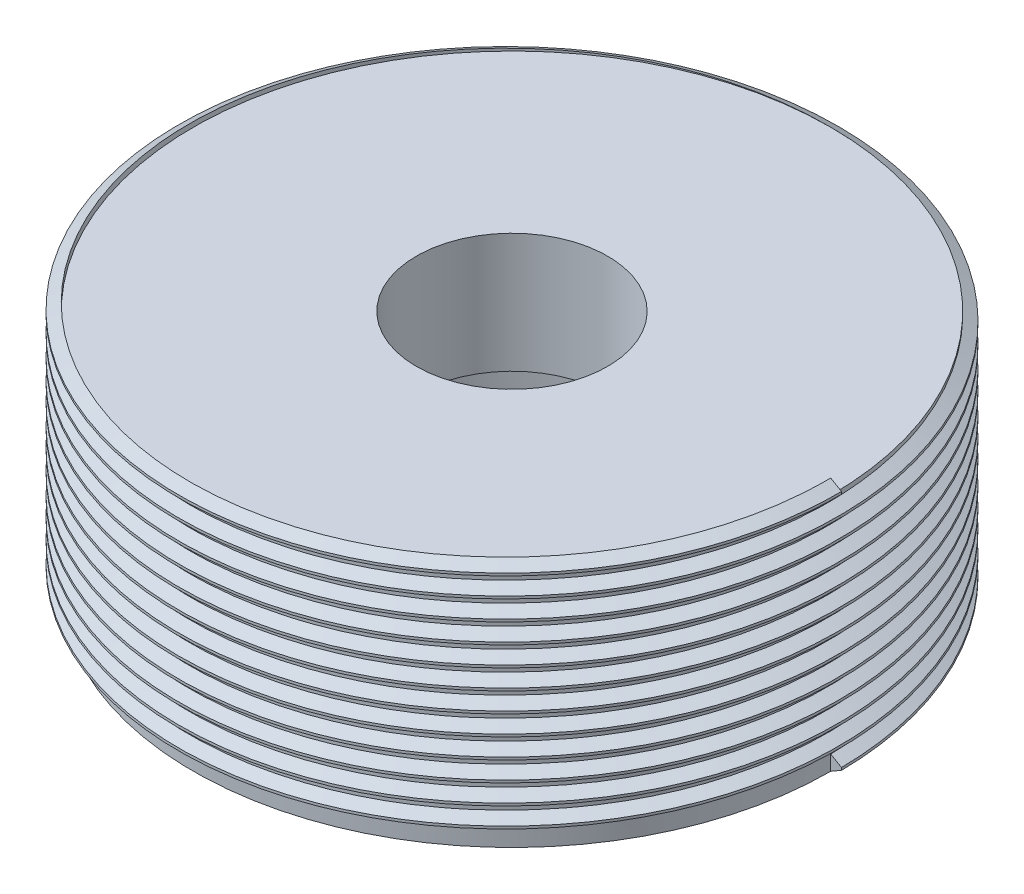
SolidWorks part; units mm, degrees
ref_plane "Front Plane" through (0, 0, 0) normal (0, 0, 1) x (1, 0, 0)
ref_plane "Top Plane" through (0, 0, 0) normal (0, 1, 0) x (1, 0, 0)
ref_plane "Right Plane" through (0, 0, 0) normal (1, 0, 0) x (0, 0, -1)
sketch "Sketch2" plane through (0, 0, 0) normal (0, 1, 0) x (1, 0, 0)
  circle A0 centre (0, 0) radius 40
extrude "Boss-Extrude1" add sketch "Sketch2" along normal blind 30
sketch "Sketch4" plane through (0, 30, 0) normal (0, 1, 0) x (1, 0, 0)
  circle A0 centre (0, 0) radius 12
extrude "Cut-Extrude1" cut sketch "Sketch4" against normal blind 15
sketch "Sketch5" plane through (0, 15, 0) normal (0, 1, 0) x (1, 0, 0)
  circle A0 centre (0, 0) radius 25
extrude "Cut-Extrude2" cut sketch "Sketch5" against normal blind 15
thread "Thread1" pitch 2.5 method extrude profile "Thread Profile1" start angle 0, offset 0, length 0, pitch 2.5, diameter 80
ref_plane "Plane1" through (40, 0, 0) normal (0, 0, 1) x (1, 0, 0)
sketch "Thread Profile1" plane through (40, 0, 0) normal (0, 0, 1) x (1, 0, 0)
  line L0 (0, 0) -> (0, 2.5) construction
  line L1 (0, 0) -> (1.3532, 0.7812)
  line L2 (1.3532, 0.7812) -> (1.3532, 1.0937)
  line L3 (1.3532, 1.0937) -> (0, 1.875)
  line L4 (1.3532, 0.9375) -> (0, 0.9375) construction
  line L11 (0, 0) -> (0, 1.875)
  point P2 (0, 0)
  dimension "Pitch" = 2.5
  dimension "Profile_Angle" = 60
  dimension "Profile_Land" = 0.3125
  dimension "Profile_Height" = 1.3532
